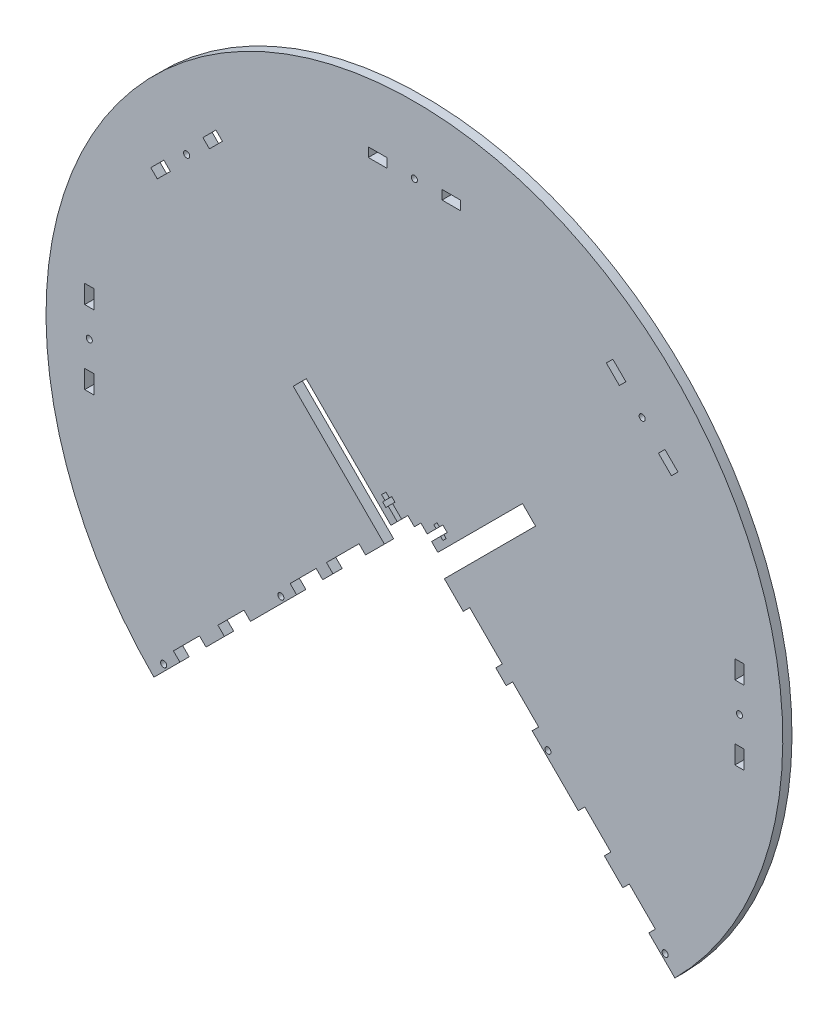
SolidWorks part; units mm, degrees
ref_plane "Front Plane" through (0, 0, 0) normal (0, 0, 1) x (1, 0, 0)
ref_plane "Top Plane" through (0, 0, 0) normal (0, 1, 0) x (1, 0, 0)
ref_plane "Right Plane" through (0, 0, 0) normal (1, 0, 0) x (0, 0, -1)
sketch "Sketch1" plane through (0, 0, 0) normal (0, 0, 1) x (1, 0, 0)
  circle A0 centre (0, -210.9923) radius 254
  arc A1 (184.0391, -386.0511) -> (248.1989, -264.9673) centre (0, -210.9923) ccw construction
extrude "Boss-Extrude1" add sketch "Sketch1" along normal blind 6.35 contours A0
sketch "Sketch3" plane through (0, 0, 0) normal (0, 0, -1) x (-1, 0, 0)
  line L0 (179.6051, -390.5974) -> (0, -210.9923)
  line L1 (0, -210.9923) -> (-179.6051, -390.5974)
  line L2 (91.3112, -302.3035) -> (113.0075, -323.9998) construction
  line L3 (-179.6051, -390.5974) -> (-172.1335, -383.1258) construction
  circle A0 centre (0, -210.9923) radius 254 construction
  arc A1 (179.6051, -390.5974) -> (-179.6051, -390.5974) centre (0, -210.9923) cw
extrude "Cut-Extrude1" cut sketch "Sketch3" against normal through all
sketch "Sketch4" plane through (0, 0, 6.35) normal (0, 0, 1) x (1, 0, 0)
  line L0 (-161.6446, -372.6369) -> (-166.1347, -368.1468)
  line L1 (-161.6446, -372.6369) -> (-143.6841, -354.6764)
  line L2 (-166.1347, -368.1468) -> (-148.1742, -350.1862)
  line L3 (-143.6841, -354.6764) -> (-148.1742, -350.1862)
  line L4 (-179.6051, -390.5974) -> (0, -210.9923) construction
  line L5 (-166.1347, -368.1468) -> (-161.6446, -372.6369) construction
  line L7 (-130.9681, -341.9603) -> (-135.4582, -337.4702)
  line L8 (-130.9681, -341.9603) -> (-113.0075, -323.9998)
  line L9 (-135.4582, -337.4702) -> (-117.4977, -319.5097)
  line L10 (-113.0075, -323.9998) -> (-117.4977, -319.5097)
  line L11 (-81.1905, -292.1828) -> (-85.6806, -287.6926)
  line L12 (-81.1905, -292.1828) -> (-63.23, -274.2223)
  line L13 (-85.6806, -287.6926) -> (-67.7201, -269.7321)
  line L14 (-63.23, -274.2223) -> (-67.7201, -269.7321)
  line L15 (-85.6806, -287.6926) -> (-81.1905, -292.1828) construction
  line L17 (-56.1266, -267.1189) -> (-60.6167, -262.6287)
  line L18 (-56.1266, -267.1189) -> (-33.676, -244.6682)
  line L19 (-60.6167, -262.6287) -> (-38.1661, -240.1781)
  line L20 (-33.676, -244.6682) -> (-38.1661, -240.1781)
  line L21 (-11.6893, -222.6816) -> (-16.1795, -218.1915)
  line L22 (-11.6893, -222.6816) -> (0, -210.9923)
  line L23 (-16.1795, -218.1915) -> (-4.4901, -206.5021)
  line L24 (0, -210.9923) -> (-4.4901, -206.5021)
  line L25 (-16.1795, -218.1915) -> (-11.6893, -222.6816) construction
  line L27 (-143.6841, -354.6764) -> (-148.1742, -350.1862) construction
  line L28 (-135.4582, -337.4702) -> (-130.9681, -341.9603) construction
  line L29 (-113.0075, -323.9998) -> (-117.4977, -319.5097) construction
  line L30 (-63.23, -274.2223) -> (-67.7201, -269.7321) construction
  line L31 (0, -210.9923) -> (-4.4901, -206.5021) construction
  line L32 (-60.6167, -262.6287) -> (-38.1661, -240.1781) construction
  line L33 (-60.6167, -262.6287) -> (-56.1266, -267.1189) construction
  line L34 (-38.1661, -240.1781) -> (-33.676, -244.6682) construction
extrude "Cut-Extrude2" cut sketch "Sketch4" against normal through all
mirror "Mirror1" about plane through (0, 0, 0) normal (1, 0, 0) of "Cut-Extrude2"
sketch "Sketch5" plane through (0, 0, 6.35) normal (0, 0, 1) x (1, 0, 0)
  line L0 (177.245, -91.8888) -> (181.7351, -87.3987)
  line L1 (-31.75, 0) -> (-19.05, 0)
  line L2 (-31.75, 0) -> (-31.75, -6.35)
  line L3 (-31.75, -6.35) -> (-19.05, -6.35)
  line L4 (-19.05, 0) -> (-19.05, -6.35)
  line L5 (19.05, 0) -> (31.75, 0)
  line L6 (19.05, 0) -> (19.05, -6.35)
  line L7 (19.05, -6.35) -> (31.75, -6.35)
  line L8 (31.75, 0) -> (31.75, -6.35)
  line L9 (-227.33, -242.7423) -> (-220.98, -242.7423)
  line L10 (-227.33, -242.7423) -> (-227.33, -230.0423)
  line L11 (-227.33, -230.0423) -> (-220.98, -230.0423)
  line L12 (-220.98, -242.7423) -> (-220.98, -230.0423)
  line L13 (-227.33, -179.2423) -> (-220.98, -179.2423)
  line L14 (-227.33, -179.2423) -> (-227.33, -191.9423)
  line L15 (-227.33, -191.9423) -> (-220.98, -191.9423)
  line L16 (-220.98, -179.2423) -> (-220.98, -191.9423)
  line L17 (220.98, -179.2423) -> (227.33, -179.2423)
  line L18 (220.98, -179.2423) -> (220.98, -191.9423)
  line L19 (220.98, -191.9423) -> (227.33, -191.9423)
  line L20 (227.33, -179.2423) -> (227.33, -191.9423)
  line L21 (220.98, -230.0423) -> (227.33, -230.0423)
  line L22 (220.98, -230.0423) -> (220.98, -242.7423)
  line L23 (220.98, -242.7423) -> (227.33, -242.7423)
  line L24 (227.33, -230.0423) -> (227.33, -242.7423)
  line L25 (177.245, -91.8888) -> (168.2647, -82.9085)
  line L26 (181.7351, -87.3987) -> (172.7548, -78.4184)
  line L27 (168.2647, -82.9085) -> (172.7548, -78.4184)
  line L28 (172.7548, -78.4184) -> (168.2647, -82.9085) construction
  line L29 (141.3239, -55.9678) -> (145.8141, -51.4776)
  line L30 (141.3239, -55.9678) -> (132.3437, -46.9875)
  line L31 (145.8141, -51.4776) -> (136.8338, -42.4974)
  line L32 (132.3437, -46.9875) -> (136.8338, -42.4974)
  line L33 (136.8338, -42.4974) -> (132.3437, -46.9875) construction
  line L34 (-177.245, -91.8888) -> (-181.7351, -87.3987)
  line L35 (-177.245, -91.8888) -> (-168.2647, -82.9085)
  line L36 (-181.7351, -87.3987) -> (-172.7548, -78.4184)
  line L37 (-168.2647, -82.9085) -> (-172.7548, -78.4184)
  line L38 (-168.2647, -82.9085) -> (-172.7548, -78.4184) construction
  line L39 (-141.3239, -55.9678) -> (-145.8141, -51.4776)
  line L40 (-141.3239, -55.9678) -> (-132.3437, -46.9875)
  line L41 (-145.8141, -51.4776) -> (-136.8338, -42.4974)
  line L42 (-132.3437, -46.9875) -> (-136.8338, -42.4974)
  line L43 (-132.3437, -46.9875) -> (-136.8338, -42.4974) construction
extrude "Cut-Extrude3" cut sketch "Sketch5" against normal through all
sketch "Sketch6" plane through (0, 0, 6.35) normal (0, 0, 1) x (1, 0, 0)
  line L0 (-189.391, -362.851) -> (-147.7076, -404.5344) construction
  line L1 (-176.6237, -378.6357) -> (-172.1335, -383.1258) construction
  line L2 (-173.6063, -375.6183) -> (-169.1162, -380.1085) construction
  line L3 (-136.5306, -343.0327) -> (-168.0044, -374.5065) construction
  line L4 (-148.1742, -350.1862) -> (-166.1347, -368.1468) construction
  line L5 (-143.6841, -354.6764) -> (-130.9681, -341.9603) construction
  line L6 (-119.5963, -271.0011) -> (-74.6896, -315.9078) construction
  line L7 (-95.8014, -297.8134) -> (-91.3112, -302.3035) construction
  line L8 (-92.784, -294.796) -> (-88.2939, -299.2862) construction
  circle A0 centre (-172.8699, -379.3721) radius 2.0955
  circle A1 centre (-92.0476, -298.5498) radius 2.0955
  dimension "D1" = 4.191
extrude "Cut-Extrude4" cut sketch "Sketch6" against normal through all
mirror "Mirror2" about plane through (0, 0, 0) normal (1, 0, 0) of "Cut-Extrude4"
sketch "Sketch7" plane through (0, 0, 6.35) normal (0, 0, 1) x (1, 0, 0)
  line L0 (170.4831, -53.7494) -> (119.6731, -104.5593) construction
  line L1 (239.3418, -210.9923) -> (189.3468, -210.9923) construction
  line L2 (0, 19.4565) -> (0, -42.3568) construction
  line L3 (-175.6943, -48.5381) -> (-146.0554, -78.1771) construction
  line L4 (-242.378, -210.9923) -> (-203.5636, -210.9923) construction
  line L5 (-2.1336, -6.35) -> (-2.1336, 0) construction
  line L6 (2.1336, -6.35) -> (2.1336, 0) construction
  line L7 (160.7931, -66.4567) -> (156.303, -70.9468) construction
  line L8 (157.7758, -63.4393) -> (153.2856, -67.9295) construction
  line L9 (220.98, -208.8714) -> (227.33, -208.8714) construction
  line L10 (220.98, -213.1132) -> (227.33, -213.1132) construction
  line L11 (-156.303, -70.9468) -> (-160.7931, -66.4567) construction
  line L12 (-153.2856, -67.9295) -> (-157.7758, -63.4393) construction
  line L13 (-227.33, -213.1132) -> (-220.98, -213.1132) construction
  line L14 (-227.33, -208.8714) -> (-220.98, -208.8714) construction
  line L15 (-224.155, -150.312) -> (-224.155, -266.4456) construction
  line L16 (-118.4045, -28.5582) -> (-198.2831, -108.4368) construction
  line L17 (-31.3546, -3.175) -> (26.462, -3.175) construction
  line L18 (131.6344, -41.7881) -> (173.4787, -83.6324) construction
  line L19 (224.155, -139.5418) -> (224.155, -241.3145) construction
  line L20 (220.98, -179.2423) -> (220.98, -191.9423) construction
  line L21 (227.33, -191.9423) -> (227.33, -179.2423) construction
  line L22 (141.3239, -55.9678) -> (132.3437, -46.9875) construction
  line L23 (145.8141, -51.4776) -> (136.8338, -42.4974) construction
  line L24 (-19.05, 0) -> (-31.75, 0) construction
  line L25 (-31.75, -6.35) -> (-19.05, -6.35) construction
  line L26 (-172.7548, -78.4184) -> (-181.7351, -87.3987) construction
  line L27 (-177.245, -91.8888) -> (-168.2647, -82.9085) construction
  line L28 (-227.33, -179.2423) -> (-227.33, -191.9423) construction
  line L29 (-220.98, -191.9423) -> (-220.98, -179.2423) construction
  circle A0 centre (-224.155, -210.9923) radius 2.0955
  circle A1 centre (-157.0394, -67.1931) radius 2.0955
  circle A2 centre (0, -3.175) radius 2.0955
  circle A3 centre (157.0394, -67.1931) radius 2.0955
  circle A4 centre (224.155, -210.9923) radius 2.0955
  dimension "D1" = 4.191
extrude "Cut-Extrude5" cut sketch "Sketch7" against normal through all
sketch "Sketch8" plane through (0, 0, 6.35) normal (0, 0, 1) x (1, 0, 0)
  line L0 (-20.6696, -231.6619) -> (-11.6893, -222.6816)
  line L1 (-20.6696, -231.6619) -> (-83.5314, -168.8001)
  line L2 (-11.6893, -222.6816) -> (-74.5511, -159.8198)
  line L3 (-83.5314, -168.8001) -> (-74.5511, -159.8198)
  line L4 (-33.676, -244.6682) -> (-11.6893, -222.6816) construction
  line L5 (-8.7612, -234.5899) -> (-94.7474, -148.6038) construction
  line L6 (-77.7195, -170.1218) -> (-52.225, -195.6163) construction
  line L7 (-73.2293, -165.6317) -> (-47.7349, -191.1262) construction
  line L8 (-16.1795, -218.1915) -> (-11.6893, -222.6816) construction
  dimension "D1" = 88.9
extrude "Cut-Extrude6" cut sketch "Sketch8" against normal through all
mirror "Mirror3" about plane through (0, 0, 0) normal (1, 0, 0) of "Cut-Extrude6"
sketch "Sketch9" plane through (0, 0, 6.35) normal (0, 0, 1) x (1, 0, 0)
  line L0 (-28.1989, -194.4827) -> (-15.046, -207.6356) construction
  line L1 (-4.4901, -206.5021) -> (0, -210.9923) construction
  line L2 (-16.1795, -218.1915) -> (-11.6893, -222.6816) construction
  line L3 (-4.4901, -206.5021) -> (-16.1795, -218.1915) construction
  line B0 (-11.8435, -213.8555) -> (-8.8261, -210.8381)
  line B1 (-17.2675, -202.3967) -> (-15.6331, -200.7623)
  line B2 (-15.6331, -200.7623) -> (-13.3881, -203.0073)
  line B3 (-13.3881, -203.0073) -> (-15.0225, -204.6417)
  line B4 (-15.0225, -204.6417) -> (-8.8261, -210.8381)
  line B5 (-17.2675, -202.3967) -> (-19.6024, -200.0618)
  line B6 (-19.6024, -200.0618) -> (-22.6198, -203.0792)
  line B7 (-20.2849, -205.4141) -> (-22.6198, -203.0792)
  line B8 (-18.0398, -207.6591) -> (-11.8435, -213.8555)
  line B9 (-19.6743, -209.2935) -> (-18.0398, -207.6591)
  line B10 (-21.9193, -207.0485) -> (-19.6743, -209.2935)
  line B11 (-20.2849, -205.4141) -> (-21.9193, -207.0485)
sketch_block_instance "TSlot-1"
sketch_block "TSlot" parameters "D1"=3.302, "D2"=3.175
extrude "Cut-Extrude7" cut sketch "Sketch9" against normal through all
mirror "Mirror4" about plane through (0, 0, 0) normal (1, 0, 0) of "Cut-Extrude7"
